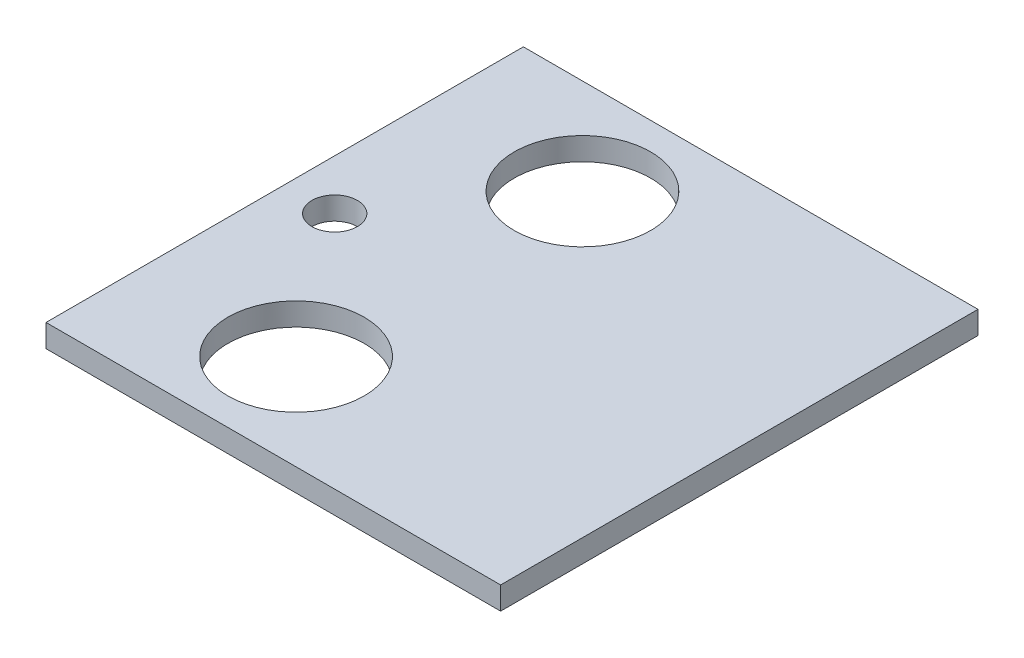
SolidWorks part; units mm, degrees
ref_plane "Front Plane" through (0, 0, 0) normal (0, 0, 1) x (1, 0, 0)
ref_plane "Top Plane" through (0, 0, 0) normal (0, 1, 0) x (1, 0, 0)
ref_plane "Right Plane" through (0, 0, 0) normal (1, 0, 0) x (0, 0, -1)
sketch "Sketch2" plane through (0, 0, 0) normal (0, 1, 0) x (1, 0, 0)
  line L0 (0, 80.9892) -> (0, -86.3988) construction
  line L1 (-50, 52.5) -> (50, 52.5)
  line L2 (-50, 52.5) -> (-50, -52.5)
  line L3 (-50, -52.5) -> (50, -52.5)
  line L4 (50, 52.5) -> (50, -52.5)
  line L5 (-89.0263, 0) -> (108.6553, 0) construction
  dimension "D1" = 100
  dimension "D2" = 105
extrude "Boss-Extrude1" add sketch "Sketch2" along normal blind 5
sketch "Sketch5" plane through (0, 0, 0) normal (0, -1, 0) x (1, 0, 0)
  line L0 (120.2435, 0) -> (-132.425, 0) construction
  line L1 (0, 87.6866) -> (0, -77.6809) construction
  line L4 (-50, 52.5) -> (50, 52.5) construction
  line L6 (-50, -52.5) -> (-50, 52.5) construction
  circle A0 centre (-39, 0) radius 39 construction
  circle A1 centre (-16.0054, 31.5) radius 15
  circle A2 centre (0, 0) radius 15 construction
  circle A4 centre (-39, 0) radius 5
  point P7 (-38.4766, 0)
  point P8 (-16.504, 31.5)
  dimension "D1" = 30
  dimension "D2" = 6
  dimension "D3" = 30
  dimension "D4" = 10
  dimension "D6" = 78
  dimension "D5" = 6
extrude "Cut-Extrude1" cut sketch "Sketch5" against normal blind 6
mirror "Mirror1" about plane through (0, 0, 0) normal (0, 0, 1) of "Cut-Extrude1"
